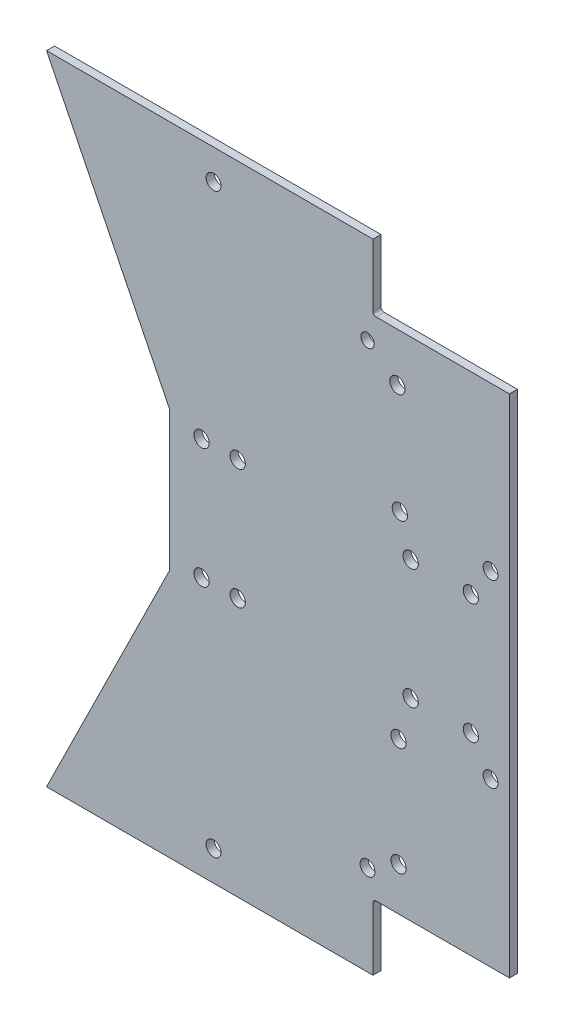
SolidWorks part; units mm, degrees
material "Thornel Mat VMA"
ref_plane "Front Plane" through (0, 0, 0) normal (0, 0, 1) x (1, 0, 0)
ref_plane "Top Plane" through (0, 0, 0) normal (0, 1, 0) x (1, 0, 0)
ref_plane "Right Plane" through (0, 0, 0) normal (1, 0, 0) x (0, 0, -1)
sketch "Sketch2" plane through (0, 0, 0) normal (0, 0, 1) x (-1, 0, 0)
  line L11 (-2.9301, 168.7083) -> (38.7094, 168.7083)
  line L12 (-2.9301, 8.6883) -> (38.7094, 8.6883)
  line L13 (38.7094, -12.1397) -> (38.7094, 8.6883)
  line L14 (143.4971, -12.1397) -> (38.7094, -12.1397)
  line L15 (38.7094, 189.5363) -> (38.7094, 168.7083)
  line L16 (143.4971, 189.5363) -> (38.7094, 189.5363)
  line L17 (104.6174, 110.8598) -> (143.4971, 189.5363)
  line L18 (104.6174, 66.5368) -> (143.4971, -12.1397)
  line L19 (104.6174, 66.5368) -> (72.8674, 66.5368)
  line L20 (72.8674, 66.5368) -> (72.8674, 110.8598)
  line L21 (104.6174, 110.8598) -> (72.8674, 110.8598)
  line L22 (-2.9301, 168.7083) -> (-2.9301, 8.6883)
  line L23 (41.9566, 19.6103) -> (41.9566, 13.2603) construction
  circle A0 centre (41.9566, 160.9613) radius 2.3495
  circle A1 centre (90.6739, 180.0113) radius 2.3495
  circle A2 centre (90.6739, -2.6147) radius 2.3495
  circle A3 centre (3.0351, 117.2098) radius 2.3495
  circle A4 centre (3.0351, 60.1868) radius 2.3495
  circle A5 centre (41.9566, 16.4353) radius 2.0955
  point P36 (41.9566, 16.4353)
  dimension "D3" = 4.699
  dimension "D7" = 31.75
  dimension "D8" = 41.6395
  dimension "D9" = 20.828
  dimension "D10" = 160.02
  dimension "D11" = 20.828
  dimension "D12" = 41.6395
  dimension "D13" = 104.7876
  dimension "D14" = 116.297
  dimension "D15" = 116.297
  dimension "D16" = 44.323
  dimension "D17" = 26.297
  dimension "D18" = 9.525
  dimension "D19" = 28.575
  dimension "D20" = 7.747
  dimension "D21" = 51.9645
  dimension "D22" = 51.4985
  dimension "D23" = 5.9651
  dimension "D24" = 51.4985
  dimension "D25" = 5.9651
  dimension "D26" = 7.747
  dimension "D27" = 3.2471
  dimension "D28" = 9.525
  dimension "D29" = 51.9645
extrude "Boss-Extrude1" add sketch "Sketch2" along normal blind 2.54
sketch "Sketch3" plane through (0, 0, 2.54) normal (0, 0, 1) x (1, 0, 0)
  line L1 (-104.6174, -66.5368) -> (-72.8674, -66.5368)
  line L2 (-104.6174, -66.5368) -> (-104.6174, -110.8598)
  line L3 (-104.6174, -110.8598) -> (-72.8674, -110.8598)
  line L4 (-72.8674, -66.5368) -> (-72.8674, -110.8598)
extrude "Boss-Extrude2" add sketch "Sketch3" against normal up to surface (2.54 mm away) up to face at (-65.9118, -88.6983, 0)
sketch "Sketch4" plane through (0, 0, 2.54) normal (0, 0, 1) x (1, 0, 0)
  line L0 (-104.6174, -66.5368) -> (-104.6174, -72.8868)
  line L1 (-104.6174, -66.5368) -> (-104.6174, -110.8598) construction
  line L2 (-104.6174, -69.7118) -> (2.9301, -69.7118) construction
  line L3 (2.9301, -168.7083) -> (2.9301, -8.6883) construction
  line L4 (-104.6174, -88.6983) -> (2.9301, -88.6983) construction
  line L5 (-104.6174, -107.6848) -> (2.9301, -107.6848) construction
  line L6 (-104.6174, -110.8598) -> (-104.6174, -104.5098)
  circle A0 centre (-94.4574, -69.7118) radius 2.413
  circle A1 centre (-83.0274, -69.7118) radius 2.413
  circle A2 centre (-28.3119, -69.7118) radius 2.413
  circle A3 centre (-9.2619, -69.7118) radius 2.413
  circle A4 centre (-9.2619, -107.6848) radius 2.413
  circle A5 centre (-28.3119, -107.6848) radius 2.413
  circle A6 centre (-83.0274, -107.6848) radius 2.413
  circle A7 centre (-94.4574, -107.6848) radius 2.413
  dimension "D2" = 10.16
  dimension "D4" = 4.826
  dimension "D5" = 4.826
  dimension "D8" = 4.826
  dimension "D9" = 4.826
  dimension "D1" = 3.175
  dimension "D3" = 11.43
  dimension "D6" = 19.05
  dimension "D7" = 12.192
extrude "Cut-Extrude1" cut sketch "Sketch4" against normal through all contours A0 | A1 | A2 | A3 | A4 | A5 | A6 | A7
sketch "Sketch5" plane through (0, 0, 2.54) normal (0, 0, 1) x (1, 0, 0)
  circle A0 centre (-31.739, -58.2731) radius 2.413
  dimension "D1" = 4.826
sketch "Sketch6" plane through (0, 0, 2.54) normal (0, 0, 1) x (1, 0, 0)
  circle A0 centre (-32.5114, -23.9918) radius 2.413
  dimension "D1" = 4.826
extrude "Cut-Extrude2" cut sketch "Sketch5" against normal through all
extrude "Cut-Extrude3" cut sketch "Sketch6" against normal through all
sketch "Sketch7" plane through (0, 0, 2.54) normal (0, 0, 1) x (1, 0, 0)
  circle A0 centre (-32.1405, -155.0714) radius 2.413
  circle A1 centre (-32.1405, -120.7814) radius 2.413
  dimension "D1" = 4.826
  dimension "D2" = 4.826
extrude "Cut-Extrude4" cut sketch "Sketch7" against normal through all
sketch "Sketch8" plane through (0, 0, 2.54) normal (0, 0, 1) x (1, 0, 0)
  line L0 (-38.7094, -168.7083) -> (2.9301, -168.7083) construction
  line L1 (-32.2387, 12.4252) -> (-40.2334, 12.4252)
  line L2 (-32.2387, 12.4252) -> (-32.2387, -8.6883)
  line L3 (-32.2387, -8.6883) -> (-40.2334, -8.6883)
  line L4 (-40.2334, 12.4252) -> (-40.2334, -8.6883)
  line L5 (-18.7398, -197.6692) -> (-40.2334, -197.6692)
  line L6 (-18.7398, -197.6692) -> (-18.7398, -168.7083)
  line L7 (-18.7398, -168.7083) -> (-40.2334, -168.7083)
  line L8 (-40.2334, -197.6692) -> (-40.2334, -168.7083)
  line L13 (-38.7094, -189.5363) -> (-38.7094, -168.7083) construction
  line L14 (2.9301, -8.6883) -> (-38.7094, -8.6883) construction
  dimension "D1" = 1.524
extrude "Cut-Extrude5" cut sketch "Sketch8" against normal through all
fillet "Fillet1" radius 1 4 edges at (-40.2334, -168.7083, 1.27) (-40.2334, -8.6883, 1.27) (-104.6174, -110.8598, 1.27) (-104.6174, -66.5368, 1.27)
